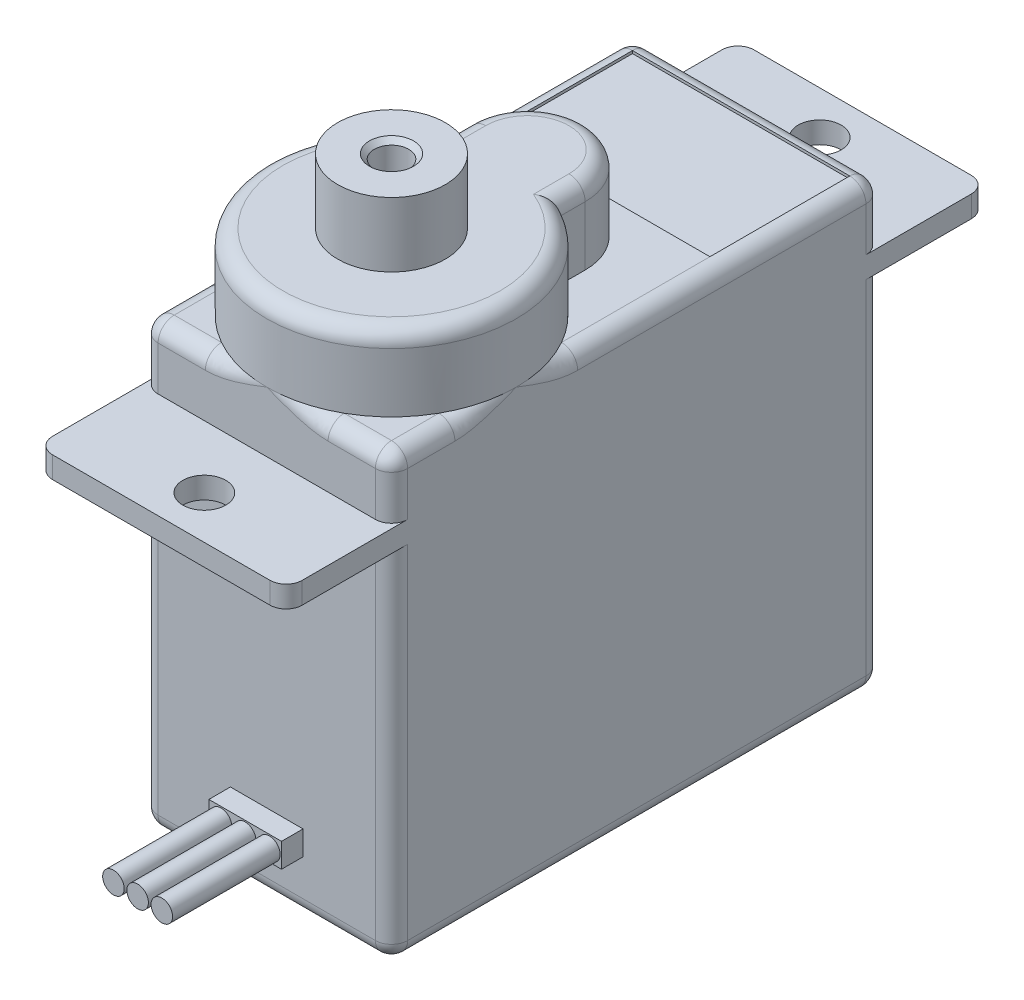
SolidWorks part; units mm, degrees
ref_plane "Front Plane" through (0, 0, 0) normal (0, 0, 1) x (1, 0, 0)
ref_plane "Top Plane" through (0, 0, 0) normal (0, 1, 0) x (1, 0, 0)
ref_plane "Right Plane" through (0, 0, 0) normal (1, 0, 0) x (0, 0, -1)
sketch "Sketch1" plane through (0, 0, 0) normal (1, 0, 0) x (0, 0, -1)
  line L1 (-11.4, -10.25) -> (11.4, -10.25)
  line L2 (-11.4, -10.25) -> (-11.4, 10.25)
  line L3 (-11.4, 10.25) -> (11.4, 10.25)
  line L4 (11.4, -10.25) -> (11.4, 10.25)
  line L5 (-11.4, -10.25) -> (11.4, 10.25) construction
  line L6 (-11.4, 10.25) -> (11.4, -10.25) construction
  point P0 (0, 0)
  dimension "D1" = 22.8
  dimension "D2" = 20.5
extrude "Boss-Extrude1" add sketch "Sketch1" along normal mid plane 11.6
sketch "Sketch2" plane through (0, 0, 0) normal (1, 0, 0) x (0, 0, -1)
  line L0 (-11.4, 10.25) -> (-11.4, -10.25) construction
  line L1 (-11.4, 7.45) -> (-16.3, 7.45)
  line L2 (-11.4, 7.45) -> (-11.4, 6.45)
  line L3 (-11.4, 6.45) -> (-16.3, 6.45)
  line L4 (-16.3, 7.45) -> (-16.3, 6.45)
  line L5 (11.4, -10.25) -> (11.4, 10.25) construction
  line L6 (11.4, 7.45) -> (16.3, 7.45)
  line L7 (11.4, 7.45) -> (11.4, 6.45)
  line L8 (11.4, 6.45) -> (16.3, 6.45)
  line L9 (16.3, 7.45) -> (16.3, 6.45)
  line L11 (-11.4, -10.25) -> (11.4, -10.25) construction
  dimension "D1" = 1
  dimension "D2" = 4.9
  dimension "D3" = 16.7
extrude "Boss-Extrude2" add sketch "Sketch2" along normal through all and the other way through all
sketch "Sketch3" plane through (0, 0, 11.4) normal (0, 0, 1) x (1, 0, 0)
  line L0 (0, 0) -> (0, -12.6847) construction
  line L2 (-1.6875, -7.8125) -> (1.6875, -7.8125)
  line L3 (-1.6875, -7.8125) -> (-1.6875, -6.6875)
  line L4 (-1.6875, -6.6875) -> (1.6875, -6.6875)
  line L5 (1.6875, -7.8125) -> (1.6875, -6.6875)
  line L6 (-1.6875, -7.8125) -> (1.6875, -6.6875) construction
  line L7 (-1.6875, -6.6875) -> (1.6875, -7.8125) construction
  line L8 (5.8, -10.25) -> (-5.8, -10.25) construction
  point P3 (0, -7.25)
  dimension "D1" = 1.125
  dimension "D2" = 3.375
  dimension "D3" = 3
extrude "Boss-Extrude3" add sketch "Sketch3" along normal blind 1
sketch "Sketch4" plane through (0, 0, 12.4) normal (0, 0, 1) x (1, 0, 0)
  line L0 (-1.6875, -7.25) -> (1.6875, -7.25) construction
  line L1 (-1.6875, -6.6875) -> (-1.6875, -7.8125) construction
  line L2 (1.6875, -7.8125) -> (1.6875, -6.6875) construction
  circle A0 centre (0, -7.25) radius 0.5
  circle A1 centre (1.125, -7.25) radius 0.5
  circle A2 centre (-1.125, -7.25) radius 0.5
  dimension "D1" = 1
  dimension "D2" = 1.125
  dimension "D3" = 1.125
extrude "Boss-Extrude5" add sketch "Sketch4" along normal blind 5
sketch "Sketch5" plane through (0, 10.25, 0) normal (0, 1, 0) x (1, 0, 0)
  line L0 (0, 0) -> (0, -19.5909) construction
  line L1 (5.8, 11.4) -> (5.8, -11.4) construction
  line L2 (5.8, -11.4) -> (-5.8, -11.4) construction
  circle A0 centre (0, -5.6) radius 5.8
extrude "Boss-Extrude6" add sketch "Sketch5" along normal blind 3.5
sketch "Sketch6" plane through (0, 10.25, 0) normal (0, 1, 0) x (1, 0, 0)
  line L0 (-5.8, 3.4) -> (5.8, 3.4) construction
  line L1 (-5.8, 11.4) -> (-5.8, -5.6) construction
  line L2 (5.8, 11.4) -> (5.8, -5.6) construction
  line L3 (5.8, 11.4) -> (-5.8, 11.4) construction
  line L4 (0, 0.7125) -> (0, 0) construction
  line L5 (2.6875, 0.7125) -> (2.6875, -1.975)
  line L6 (2.6875, -1.975) -> (-2.6875, -1.975)
  line L7 (-2.6875, -1.975) -> (-2.6875, 0.7125)
  arc A0 (2.6875, 0.7125) -> (-2.6875, 0.7125) centre (0, 0.7125) ccw
  dimension "D1" = 5.375
  dimension "D2" = 8
extrude "Boss-Extrude7" add sketch "Sketch6" along normal up to surface (3.5 mm away) up to face at (0, 13.75, 11.4)
sketch "Sketch7" plane through (0, 13.75, 0) normal (0, 1, 0) x (1, 0, 0)
  circle A0 centre (0, -5.6) radius 2.5
  dimension "D1" = 5
extrude "Boss-Extrude8" add sketch "Sketch7" along normal blind 3
sketch "Sketch8" plane through (0, 7.45, 0) normal (0, 1, 0) x (1, 0, 0)
  line L0 (0, 14.3) -> (0, -14.3) construction
  circle A0 centre (0, 14.3) radius 1
  circle A1 centre (0, -14.3) radius 1
  dimension "D1" = 2
  dimension "D2" = 28.6
extrude "Cut-Extrude1" cut sketch "Sketch8" against normal up to next
fillet "Fillet1" radius 0.75 27 edges at (2.6875, 13.75, -0.1261) (-2.6875, 13.75, -0.1261) (-5.8, 10.25, -2.9) (-2.9, 10.25, 11.4) (5.8, 10.25, -2.9) (0, 13.75, -3.4) (0, 13.75, 11.4) (0, 10.25, -11.4) (-5.8, -10.25, 0) (0, -10.25, -11.4) (5.8, -10.25, 0) (0, -10.25, 11.4) (-5.8, 10.25, 8.5) (2.9, 10.25, 11.4) (5.8, 10.25, 8.5) (-5.8, 6.95, 16.3) (5.8, 6.95, 16.3) (5.8, 6.95, -16.3) (-5.8, 6.95, -16.3)
sketch "Sketch9" plane through (0, 10.25, 0) normal (0, 1, 0) x (1, 0, 0)
  line L0 (-5.05, 10.65) -> (-5.05, -2.7474) construction
  line L1 (5.05, -2.7474) -> (5.05, 10.65) construction
  line L2 (5.05, 10.65) -> (-5.05, 10.65) construction
  line L3 (-5.05, 10.65) -> (-5.05, 4.15)
  line L4 (5.05, 4.15) -> (5.05, 10.65)
  line L5 (5.05, 10.65) -> (-5.05, 10.65)
  line L6 (5.05, 4.15) -> (-5.05, 4.15)
  dimension "D1" = 6.5
extrude "Cut-Extrude2" cut sketch "Sketch9" against normal blind 0.125
hole_wizard "M2x0.4 Tapped Hole1" positions "Sketch10" profile "Sketch11" tap size "M2x0.4" standard "ANSI Metric"
sketch "Sketch10" plane through (0, 16.75, 0) normal (0, 1, 0) x (1, 0, 0)
  point P0 (0, -5.6)
sketch "Sketch11" plane through (0, 16.75, 5.6) normal (1, 0, 0) x (0, 0, 1)
  line L0 (0, 0) -> (0, 5.6807)
  line L1 (0, 5.6807) -> (0.8, 5.2)
  line L2 (0.8, 5.2) -> (0.8, 0.225)
  line L3 (0.8, 0.225) -> (1.025, 0)
  line L5 (1.025, 0) -> (0, 0)
  line L6 (-0.8, 0.225) -> (-1.025, 0) construction
  line L10 (0, 5.6807) -> (-0.8, 5.2) construction
  line L11 (0, -6.35) -> (0, 107.95) construction
  dimension "Tap Drill Dia." = 1.6
  dimension "Tap Drill Depth" = 5.2
  dimension "Near C'Sink Dia." = 2.05
  dimension "Near C'Sink Angle" = 90
  dimension "Drill Angle" = 118
cosmetic thread "Hole Thread1" parameters "D1"=4, "D2"=2
equation "\"D3@Sketch4\"=\"D2@Sketch4\""
